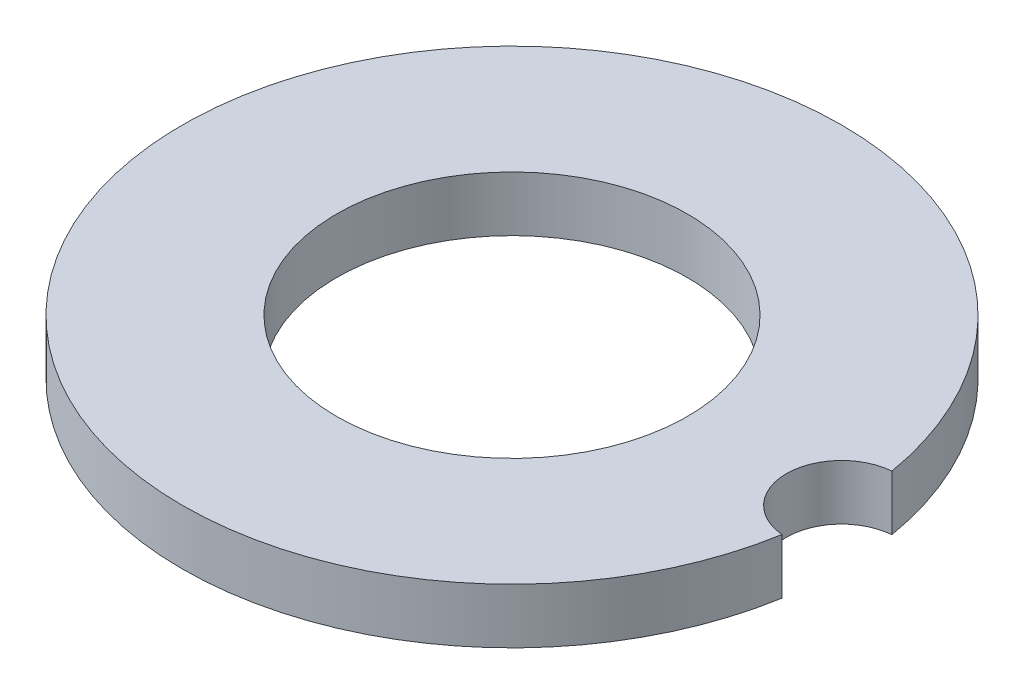
SolidWorks part; units mm, degrees
ref_plane "Front Plane" through (0, 0, 0) normal (0, 0, 1) x (1, 0, 0)
ref_plane "Top Plane" through (0, 0, 0) normal (0, 1, 0) x (1, 0, 0)
ref_plane "Right Plane" through (0, 0, 0) normal (1, 0, 0) x (0, 0, -1)
sketch "Sketch1" plane through (0, 0, 0) normal (0, 1, 0) x (1, 0, 0)
  circle A0 centre (0, 0) radius 40.4114
  circle A1 centre (0, 0) radius 75.9206
  dimension "Front_CR_ID" = 80.8228
  dimension "Front_CR_OD" = 151.8412
extrude "Boss-Extrude1" add sketch "Sketch1" along normal blind 12.7 contours A1
extrude "Cut-Extrude2" cut sketch "Sketch1<10>" along normal through all contours A0
sketch "Sketch1<10>" plane through (0, 0, 0) normal (0, 1, 0) x (1, 0, 0) same geometry as "Sketch1"
sketch "Sketch2" plane through (0, 12.7, 0) normal (0, 1, 0) x (1, 0, 0)
  line L0 (76.2, 12.7) -> (76.2, -12.7)
  arc A0 (76.2, 12.7) -> (76.2, -12.7) centre (75.9206, 0) ccw
  circle A1 centre (0, 0) radius 75.9206 construction
  dimension "D1" = 25.4
extrude "Cut-Extrude3" cut sketch "Sketch2" against normal through all contours A0 L0
ref_plane "Plane1" through (0, 6.35, 0) normal (0, -1, 0) x (-1, 0, 0)
equation "\"Bodytube_OD\" = 6.17in"
equation "\"Bodytube_ID\" = 5.998in"
equation "\"Motor_OD\" = 4in"
equation "\"Fwd_Tube_Length\" = 38in"
equation "\"Mid_Tube_Length\" = 8in"
equation "\"Aft_Section_Length\"= 40in"
equation "\"Mid_Coupler_Length\" = 13in"
equation "\"Aft_Lower_Length\"= 22in"
equation "\"AB_Coupler_OD_Length\"= 1in"
equation "\"AB_Coupling_Section_Length\"= 0.375in"
equation "\"AB_Coupler_Length\"= \"AB_Coupler_OD_Length\" + \"AB_Coupling_Section_Length\" * 2"
equation "\"Cutout_Angle\" = 80"
equation "\"AB_Paddle_Height\" = 0.375in"
equation "\"AB_Coupler_Num_Screws\"= 6"
equation "\"Num_Cutouts\" = 3"
equation "\"AB_Coupler_OD\"= 6.17in"
equation "\"AB_Coupler_ID\"= 5.75in"
equation "\"AB_Coupler_Surface_Diameter\"= 5.998in"
equation "\"AB_Coupling_Screw_Diameter\"= 0.1065in"
equation "\"AB_Central_Bushing_Length\" = .75in"
equation "\"Lead_Screw_Dist\" = 2.25in"
equation "\"Lead_Screw_Diam\" = (27/64)*1in"
equation "\"Lead_Screw_Length\" = (\"Mid_Coupler_Length\" + 2*0.375in + 2*0.5in)"
equation "\"Paddle_Pin_Offset\" = .25in"
equation "\"Paddle_Pin_Radius\" = 2.25in"
equation "\"Paddle_Gear_OD\" = 3.2in"
equation "\"Fwd_BKHD_From_Top\" = 18in"
equation "\"Front_CR_OD@Sketch1\" = \"Bodytube_ID\" - 0.02"
equation "\"Front_CR_ID@Sketch1\"= 3.162 + 0.02"
